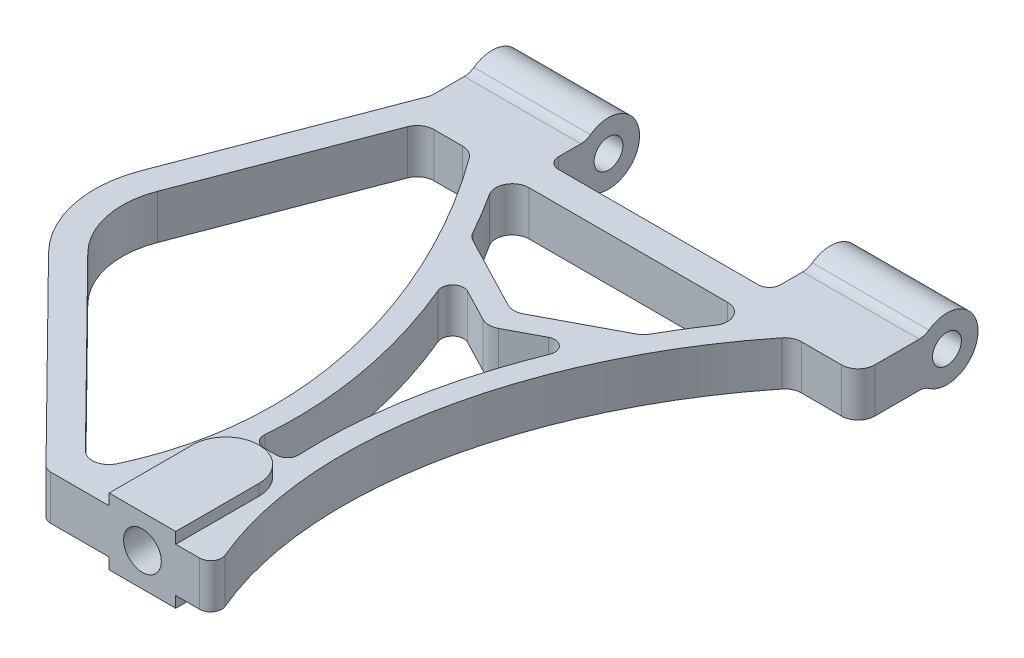
SolidWorks part; units mm, degrees
material "7050-T73510"
ref_plane "前视基准面" through (0, 0, 0) normal (0, 0, 1) x (1, 0, 0)
ref_plane "上视基准面" through (0, 0, 0) normal (0, 1, 0) x (1, 0, 0)
ref_plane "右视基准面" through (0, 0, 0) normal (1, 0, 0) x (0, 0, -1)
sketch "草图1" plane through (0, 0, 0) normal (0, 1, 0) x (1, 0, 0)
  line L0 (0, 0) -> (0, -71.0588) construction
  line L1 (-41, 0) -> (41, 0)
  line L2 (41, 0) -> (41, -15)
  line L3 (-20, -15) -> (20, -15)
  line L4 (20, -15) -> (20, 0)
  line L5 (-20, -15) -> (-20, 0)
  line L6 (-41, 0) -> (-41, -15)
  line L7 (-41, -15) -> (-55.4151, -52.7809)
  line L8 (-50.9683, -73.9547) -> (-17.3894, -108)
  line L9 (17.3894, -108) -> (-17.3894, -108)
  line L10 (-37.5561, -20) -> (-50.7436, -54.5633)
  line L11 (-47.4085, -70.4436) -> (-13.8296, -104.4889)
  line L12 (-20, -20) -> (20, -20)
  line L13 (-20, -20) -> (-37.5561, -20)
  line L14 (-36.3285, -16.7824) -> (-50.7436, -54.5633) construction
  line L15 (20, -20) -> (29.3367, -20)
  line L16 (29.3367, -20) -> (41, -20)
  line L17 (41, -20) -> (41, -15)
  line L18 (17.3894, -108) -> (17.3894, -103.9952)
  line L19 (17.3894, -103.9952) -> (11.6436, -103.9952)
  arc A0 (-55.4151, -52.7809) -> (-50.9683, -73.9547) centre (-36.729, -59.9104) ccw
  arc A1 (-50.7436, -54.5633) -> (-47.4085, -70.4436) centre (-36.729, -59.9104) ccw
  arc A2 (-55.4151, -52.7809) -> (-50.9683, -73.9547) centre (-36.729, -59.9104) ccw construction
  spline S0 degree 3 poles (-28.7781, -20) (-11.3984, -43.1807) (1.8161, -77.3261) (-13.8296, -104.4889) knots 0 0 0 0 1 1 1 1
  spline S1 degree 3 poles (29.3367, -20) (14.953, -37.359) (2.8941, -68.3029) (9.4113, -98.9865) (12.7561, -106.6788) (13.3872, -108) knots 0 0 0 0 0.771164 1 1.048078 1.048078 1.048078 1.048078
  point P7 (0, 0)
  point P11 (0, -15)
  point P18 (0, -108)
  point P21 (-60, -64.7976)
  dimension "D6" = 20
  dimension "D1" = 82
  dimension "D2" = 15
  dimension "D3" = 40
  dimension "D4" = 108
  dimension "D5" = 60
  dimension "D7" = 5
  dimension "D8" = 5
extrude "凸台-拉伸1" add sketch "草图1" along normal mid plane 8 contours S1 S0 L11 A1 L10 L13 L16 L17 L2 L1 L4 L3 L5 L6 L7 A0 L8 L9 region at (-5.7488, 0, 44.6388)
fillet "圆角1" radius 4 4 edges at (-30.5, 4, 0) (-30.5, -4, 0) (30.5, -4, 0) (30.5, 4, 0)
sketch "草图4" plane through (41, 0, 0) normal (1, 0, 0) x (0, 0, -1)
  circle A0 centre (-4, 0) radius 2.6
  dimension "D1" = 5.2
extrude "切除-拉伸1" cut sketch "草图4" against normal through all
fillet "圆角2" radius 3 5 edges at (-41, 0, 15) (-28.7781, 0, 20) (-37.5561, 0, 20) (41, 0, 20) (29.3367, 0, 20)
fillet "圆角3" radius 3 1 edges at (-13.8296, 0, 104.4889)
sketch "草图5" plane through (0, 4, 0) normal (0, 1, 0) x (1, 0, 0)
  line L0 (0, 0) -> (0, -135.1291) construction
sketch "草图6" plane through (0, 0, 0) normal (0, 1, 0) x (1, 0, 0)
  line L0 (0, 0) -> (0, -135.1291) construction
  line L1 (-6, -93) -> (-6, -108)
  line L2 (13.3872, -108) -> (-17.3894, -108) construction
  line L3 (-6, -108) -> (6, -108)
  line L4 (6, -108) -> (6, -93)
  circle A0 centre (0, -93) radius 6
  dimension "D1" = 12
  dimension "D2" = 15
extrude "凸台-拉伸3" add sketch "草图6" along normal mid plane 12 contours A0 L1 L3 L4 | A0 region at (0, 0, 102.769) region at (0, 0, 93)
sketch "草图9" plane through (0, 4, 0) normal (0, 1, 0) x (1, 0, 0)
  line L0 (0, 0) -> (0, -85) construction
  line L1 (-3.3016, -85) -> (3.279, -85)
  line L2 (-23.4649, -20.5) -> (23.8271, -20.5)
  line L3 (-20, -15) -> (20, -15) construction
  spline S2 degree 3 poles (1317.0811, -1496.9816) (-347.0001, 75.5942) (-76.3606, 89.2784) (-9.9341, -44.2006) (-7.1858, -51.2673) (-4.4289, -62.1488) (-3.738, -65.823) (-2.9035, -73.2122) (-2.7601, -76.9276) (-3.1169, -84.3382) (-3.6175, -88.0337) (-28.823, -193.699) (-342.5398, -258.0351) (-1824.8793, 695.5323) knots -4.497753 -4.497753 -4.497753 -4.497753 0.25 0.25 0.5 0.5 0.625 0.625 0.75 0.75 0.875 0.875 4.371018 4.371018 4.371018 4.371018 only from (-24.6389, -18.8684) to (-8.2479, -102.435)
  spline S3 degree 3 poles (-23.4649, -20.5) (-19.7453, -25.7528) (-16.2653, -31.4786) (-9.9341, -44.2006) (-7.1858, -51.2673) (-4.4289, -62.1488) (-3.738, -65.823) (-2.9035, -73.2122) (-2.7601, -76.9276) (-3.0087, -82.0909) (-3.1287, -83.5474) (-3.3016, -85) knots 0.02366 0.02366 0.02366 0.02366 0.25 0.25 0.5 0.5 0.625 0.625 0.75 0.75 0.799186 0.799186 0.799186 0.799186
  spline S5 degree 3 poles (-309.8237, -1967.0787) (446.3775, 75.5177) (79.1437, 100.6634) (9.0759, -46.2546) (6.4124, -54.0233) (3.19, -69.9402) (2.6314, -78.0907) (3.7491, -90.1807) (4.448, -94.1876) (36.5728, -214.0468) (377.1129, -274.8017) (1741.354, 847.8027) knots -4.520777 -4.520777 -4.520777 -4.520777 0.25 0.25 0.5 0.5 0.75 0.75 0.875 0.875 4.549676 4.549676 4.549676 4.549676 only from (25.3034, -18.6164) to (9.7778, -109.724)
  spline S6 degree 3 poles (23.8271, -20.5) (19.505, -26.1516) (15.7013, -32.3625) (9.0759, -46.2546) (6.4124, -54.0233) (3.2667, -69.5616) (2.6869, -77.3158) (3.279, -85) knots 0.025253 0.025253 0.025253 0.025253 0.25 0.25 0.5 0.5 0.738109 0.738109 0.738109 0.738109
  dimension "D3" = 85
  dimension "D4" = 5.5
  dimension "D1" = 4
  dimension "D2" = 4
extrude "切除-拉伸2" cut sketch "草图9" against normal blind 12
fillet "圆角4" radius 3 2 edges
fillet "圆角5" radius 2 2 edges
fillet "圆角6" radius 2 2 edges at (-20, 0, 15) (20, 0, 15)
sketch "草图10" plane through (0, 4, 0) normal (0, 1, 0) x (1, 0, 0)
  line L0 (-16.6834, -35) -> (0, -43.688)
  line L1 (0, -43.688) -> (16.469, -35)
  line L2 (-16.6834, -35) -> (16.469, -35) construction
  line L3 (0, -43.688) -> (0, 0) construction
  line L4 (-17.6072, -36.7739) -> (0.006, -45.9461)
  line L5 (0.006, -45.9461) -> (17.4022, -36.7689)
  line L6 (-15.7596, -33.2261) -> (-0.006, -41.43)
  line L7 (-0.006, -41.43) -> (15.5358, -33.2311)
  line L8 (-15.7596, -33.2261) -> (-17.6072, -36.7739)
  line L9 (15.5358, -33.2311) -> (17.4022, -36.7689)
  dimension "D1" = 35
  dimension "D2" = 2
  dimension "D3" = 2
extrude "凸台-拉伸5" add sketch "草图10" against normal up to surface (8 mm away) contours L6 L7 L9 L5 L4 L8 up to face at (-2.1087, -4, 53.3031)
fillet "圆角7" radius 2 2 edges
fillet "圆角8" radius 3 4 edges at (0.006, 0, 45.9461) (-0.006, 0, 41.43)
fillet "圆角9" radius 2 1 edges at (13.3872, 0, 108)
fillet "圆角10" radius 2 1 edges at (-17.3894, 0, 108)
sketch "草图11" plane through (0, 0, 108) normal (0, 0, 1) x (1, 0, 0)
  circle A0 centre (0, 0) radius 3
  dimension "D1" = 6
extrude "切除-拉伸3" cut sketch "草图11" against normal blind 19
hole_wizard "M8 螺纹孔3" positions "3D草图2" profile "草图13" tap size "M8" standard "GB"
sketch3d "3D草图2"
  line L0 (0, 0, 89) -> (0, 0, 108) construction
  point P0 (0, 0, 108)
cosmetic thread "孔螺蚊线1" parameters "D1"=12, "D2"=8
sketch "草图13" plane through (0, 0, 108) normal (1, 0, 0) x (0, -1, 0)
  line L0 (0, 0) -> (0, 17.0429)
  line L1 (0, 17.0429) -> (3.4, 15)
  line L2 (3.4, 15) -> (3.4, 0)
  line L5 (3.4, 0) -> (0, 0)
  line L10 (0, 17.0429) -> (-3.4, 15) construction
  line L11 (0, -6.35) -> (0, 107.95) construction
  dimension "螺纹孔钻头直径" = 6.8
  dimension "螺纹孔钻头深度" = 15
  dimension "导头角度" = 118
sketch "草图14" plane through (41, 0, 0) normal (1, 0, 0) x (0, 0, -1)
  circle A0 centre (-4, 0) radius 2.6 construction
  circle A1 centre (-4, 0) radius 2.6
  circle A2 centre (-4, 0) radius 5.6
  dimension "D1" = 3
extrude "凸台-拉伸6" add sketch "草图14" against normal up to surface (21 mm away) up to face at (20, 0, 6.6)
sketch "草图15" plane through (-41, 0, 0) normal (-1, 0, 0) x (0, 0, 1)
  circle A1 centre (4, 0) radius 5.6
  circle A2 centre (4, 0) radius 5.6
  circle A3 centre (4, 0) radius 2.6
  circle A4 centre (4, 0) radius 2.6
  dimension "D1" = 0
  dimension "D2" = 0
extrude "凸台-拉伸7" add sketch "草图15" against normal up to surface (21 mm away) up to face at (-20, 0, 6.6)
fillet "圆角11" radius 3 4 edges at (30.5, -4, 7.9192) (-30.5, -4, 7.9192) (-30.5, 4, 7.9192) (30.5, 4, 7.9192)
sketch "草图16" plane through (0, 0, 0) normal (0, 1, 0) x (1, 0, 0)
  line L0 (-47.4085, -70.4436) -> (-13.8296, -104.4889) construction
  line L1 (-37.5561, -20) -> (-50.7436, -54.5633) construction
  line L2 (-20, -20) -> (-37.5561, -20) construction
  line L3 (-20, -20) -> (20, -20) construction
  line L4 (20, -20) -> (29.3367, -20) construction
  line L5 (29.3367, -20) -> (41, -20) construction
  line L6 (41, -20) -> (41, -15) construction
  line L7 (41, 0) -> (41, -15) construction
  line L8 (-41, 0) -> (41, 0) construction
  line L9 (-41, 0) -> (-41, -15) construction
  line L10 (-41, -15) -> (-55.4151, -52.7809) construction
  line L11 (-50.9683, -73.9547) -> (-17.3894, -108) construction
  line L12 (17.3894, -108) -> (-17.3894, -108) construction
  line L13 (17.3894, -108) -> (17.3894, -103.9952) construction
  line L14 (17.3894, -103.9952) -> (11.6436, -103.9952) construction
  line L15 (20, -15) -> (20, 0) construction
  line L16 (-20, -15) -> (20, -15) construction
  line L17 (-20, -15) -> (-20, 0) construction
  line L18 (-47.4085, -70.4436) -> (-16.7175, -101.5609)
  line L19 (-38.2927, -21.9306) -> (-50.7436, -54.5633)
  line L20 (-20, -20) -> (-37.5561, -20)
  line L21 (-20, -20) -> (20, -20)
  line L22 (20, -20) -> (29.3367, -20)
  line L23 (29.3367, -20) -> (41, -20)
  line L24 (41, -20) -> (41, -15)
  line L25 (41, 0) -> (41, -15)
  line L26 (-41, 0) -> (41, 0)
  line L27 (-41, 0) -> (-41, -15)
  line L28 (-41.1971, -15.5166) -> (-55.4151, -52.7809)
  line L29 (-50.9683, -73.9547) -> (-17.3894, -108)
  line L30 (17.3894, -108) -> (-17.3894, -108)
  line L31 (17.3894, -108) -> (17.3894, -103.9952)
  line L32 (17.3894, -103.9952) -> (11.6436, -103.9952)
  line L33 (20, -15) -> (20, 0)
  line L34 (-20, -15) -> (20, -15)
  line L35 (-20, -15) -> (-20, 0)
  line L36 (-41, -15) -> (-41, -20)
  line L37 (-41, -20) -> (-37.5561, -20)
  arc A0 (-50.7436, -54.5633) -> (-47.4085, -70.4436) centre (-36.729, -59.9104) ccw construction
  arc A1 (-55.4151, -52.7809) -> (-50.9683, -73.9547) centre (-36.729, -59.9104) ccw construction
  arc A2 (-50.7436, -54.5633) -> (-47.4085, -70.4436) centre (-36.729, -59.9104) ccw
  arc A3 (-55.4151, -52.7809) -> (-50.9683, -73.9547) centre (-36.729, -59.9104) ccw
  arc A4 (-35.4898, -20) -> (-38.2927, -21.9306) centre (-35.4898, -23) ccw construction
  arc A5 (-35.4898, -20) -> (-38.2927, -21.9306) centre (-35.4898, -23) ccw
  arc A6 (-41.1971, -15.5166) -> (-41, -14.4471) centre (-44, -14.4471) ccw construction
  arc A7 (-41.1971, -15.5166) -> (-41, -14.4471) centre (-44, -14.4471) ccw
  arc A8 (-16.7175, -101.5609) -> (-11.8672, -100.7317) centre (-14.5816, -99.4543) ccw construction
  arc A9 (-16.7175, -101.5609) -> (-11.8672, -100.7317) centre (-14.5816, -99.4543) ccw
  spline S0 degree 3 poles (1264.9721, -1540.5209) (-1796.9741, 1558.8184) (1947.3589, -1265.7007) (-1919.8222, 464.0898) knots -4.114199 -4.114199 -4.114199 -4.114199 4.243669 4.243669 4.243669 4.243669 only from (-28.7781, -20) to (-13.8296, -104.4889) construction
  spline S1 degree 3 poles (-383.5414, -1957.2634) (506.9911, 280.3415) (-25.5267, 65.5043) (33.0581, -210.317) (410.6767, -239.7434) (1801.3092, 746.0296) knots -4.570526 -4.570526 -4.570526 -4.570526 0.771164 1 4.850856 4.850856 4.850856 4.850856 only from (29.3367, -20) to (13.3872, -108) construction
  spline S2 degree 3 poles (-28.7781, -20) (-10.6408, -44.1912) (2.9603, -80.3239) (-16.0423, -108) knots 0 0 0 0 1.043593 1.043593 1.043593 1.043593
  spline S3 degree 3 poles (29.3367, -20) (14.953, -37.359) (2.8941, -68.3029) (9.4113, -98.9865) (12.7561, -106.6788) (13.3872, -108) knots 0 0 0 0 0.771164 1 1.048078 1.048078 1.048078 1.048078
extrude "切除-拉伸4" [suppressed] cut sketch "草图16" against normal mid plane 68 contours S2 L18 A2 L19 L37 L36 L28 A3 L29 L30
fillet "圆角12" [suppressed] radius 2
fillet "圆角13" [suppressed] radius 3
